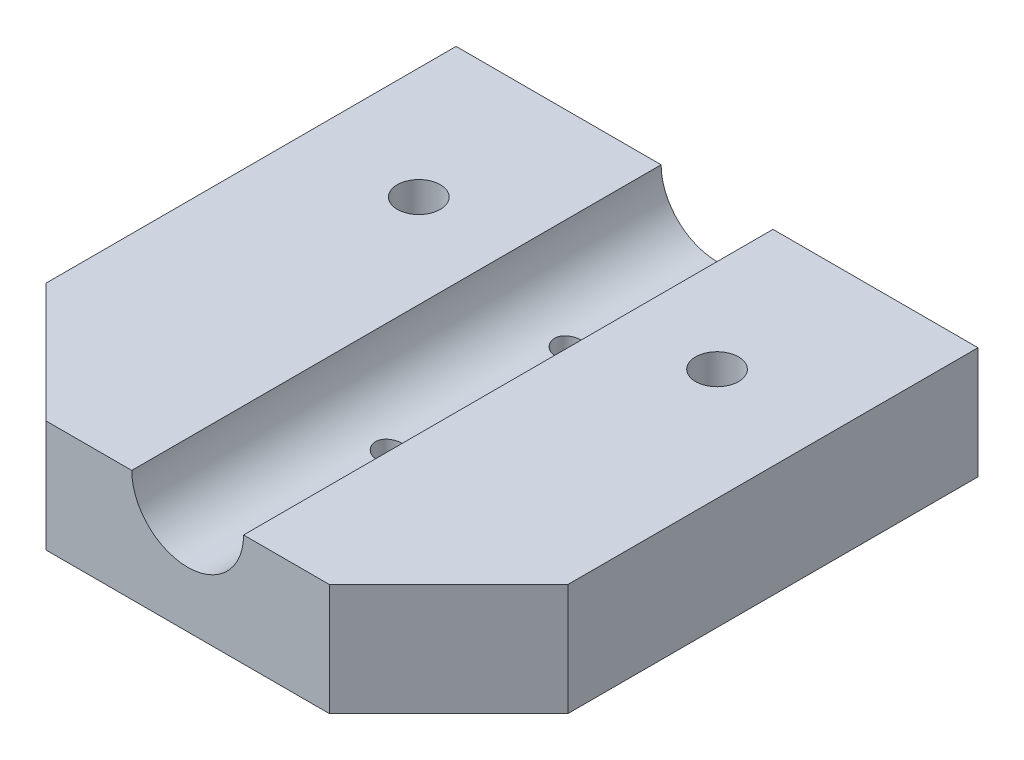
SolidWorks part; units mm, degrees
material "Nylon 6/10"
ref_plane "Front Plane" through (0, 0, 0) normal (0, 0, 1) x (1, 0, 0)
ref_plane "Top Plane" through (0, 0, 0) normal (0, 1, 0) x (1, 0, 0)
ref_plane "Right Plane" through (0, 0, 0) normal (1, 0, 0) x (0, 0, -1)
sketch "Sketch1" plane through (0, 0, 0) normal (0, 1, 0) x (1, 0, 0)
  line L1 (-22.225, -22.5425) -> (22.225, -22.5425)
  line L2 (-22.225, -22.5425) -> (-22.225, 22.5425)
  line L3 (-22.225, 22.5425) -> (22.225, 22.5425)
  line L4 (22.225, -22.5425) -> (22.225, 22.5425)
  line L5 (-22.225, -22.5425) -> (22.225, 22.5425) construction
  line L6 (-22.225, 22.5425) -> (22.225, -22.5425) construction
  point P0 (0, 0)
  dimension "D1" = 45.085
  dimension "D2" = 44.45
extrude "Boss-Extrude1" add sketch "Sketch1" along normal blind 9.525
sketch "Sketch4" plane through (0, 0, 22.5425) normal (0, 0, 1) x (1, 0, 0)
  line L0 (-22.225, 9.525) -> (22.225, 9.525) construction
  circle A0 centre (0, 9.525) radius 4.7625
  dimension "D1" = 9.525
extrude "Cut-Extrude1" cut sketch "Sketch4" against normal through all
hole_wizard "MotorHoles" positions "Sketch3" profile "Sketch2" tap size "#4-40" standard "ANSI Inch"
sketch "Sketch3" plane through (0, 0, 0) normal (0, -1, 0) x (-1, 0, 0)
  line L0 (22.225, -22.5425) -> (-22.225, -22.5425) construction
  line L2 (0, 0) -> (0, -31.1437) construction
  point P0 (-5.715, -19.3675)
  point P2 (5.715, -19.3675)
  dimension "D1" = 3.175
  dimension "D2" = 11.43
cosmetic thread "Hole Thread1" parameters "D1"=5.588, "D2"=2.8448
cosmetic thread "Hole Thread2" parameters "D1"=5.588, "D2"=2.8448
sketch "Sketch2" plane through (5.715, 0, 19.3675) normal (1, 0, 0) x (0, 0, -1)
  line L0 (0, 0) -> (0, 7.0292)
  line L1 (0, 7.0292) -> (1.1303, 6.35)
  line L2 (1.1303, 6.35) -> (1.1303, 0)
  line L5 (1.1303, 0) -> (0, 0)
  line L10 (0, 7.0292) -> (-1.1303, 6.35) construction
  line L11 (0, -6.35) -> (0, 107.95) construction
  dimension "Tap Drill Dia." = 2.2606
  dimension "Tap Drill Depth" = 6.35
  dimension "Drill Angle" = 118
hole_wizard "CBORE for #6 Socket Head Cap Screw1" positions "Sketch6" profile "Sketch5" counterbore size "#6" standard "ANSI Inch" end condition through all
sketch "Sketch6" plane through (0, 0, 0) normal (0, -1, 0) x (-1, 0, 0)
  line L0 (0, 0) -> (0, 20.3228) construction
  line L2 (-22.225, 22.5425) -> (22.225, 22.5425) construction
  point P0 (-12.7, 9.8425)
  point P2 (12.7, 9.8425)
  dimension "D1" = 25.4
  dimension "D2" = 12.7
sketch "Sketch5" plane through (12.7, 0, -9.8425) normal (1, 0, 0) x (0, 0, -1)
  line L0 (0, 0) -> (0, 9.525)
  line L1 (0, 9.525) -> (1.8288, 9.525)
  line L3 (1.8288, 9.525) -> (1.8288, 3.5052)
  line L4 (3.5725, 3.5052) -> (1.8288, 3.5052)
  line L5 (3.5725, 3.5052) -> (3.5725, 0.635)
  line L6 (3.5725, 0.635) -> (4.2075, 0)
  line L7 (4.2075, 0) -> (0, 0)
  line L8 (-3.5725, 0.635) -> (-4.2075, 0) construction
  line L11 (0, -6.35) -> (0, 107.95) construction
  dimension "Thru Hole Dia." = 3.6576
  dimension "Thru Hole Depth" = 9.525
  dimension "C'Bore Dia." = 7.145
  dimension "C'Bore Depth" = 3.5052
  dimension "Near C'Sink Dia." = 8.415
  dimension "Near C'Sink Angle" = 90
chamfer "Chamfer1" distance 10.16 angle 45 2 edges at (22.225, 4.7625, 22.5425) (-22.225, 4.7625, 22.5425)
hole_wizard "#4-40 Tapped Hole1" positions "Sketch8" profile "Sketch7" tap size "#4-40" standard "ANSI Inch" end condition through all
sketch "Sketch8" plane through (0, 0, 0) normal (0, -1, 0) x (-1, 0, 0)
  line L0 (0, 0) -> (0, 3.4708) construction
  line L2 (-12.7, 9.8425) -> (12.7, 9.8425) construction
  point P0 (0, 9.8425)
  point P2 (0, -5.3975)
  dimension "D1" = 15.24
sketch "Sketch7" plane through (0, 0, -9.8425) normal (1, 0, 0) x (0, 0, -1)
  line L0 (0, 0) -> (0, 9.525)
  line L1 (0, 9.525) -> (1.1303, 9.525)
  line L2 (1.1303, 9.525) -> (1.1303, 0)
  line L5 (1.1303, 0) -> (0, 0)
  line L11 (0, -6.35) -> (0, 107.95) construction
  dimension "Thru Tap Drill Dia." = 2.2606
  dimension "Thru Tap Drill Depth" = 9.525
cosmetic thread "Hole Thread3" parameters "D2"=2.8448
cosmetic thread "Hole Thread4" parameters "D2"=2.8448
chamfer "Chamfer3" [suppressed] distance 5.08 angle 45
